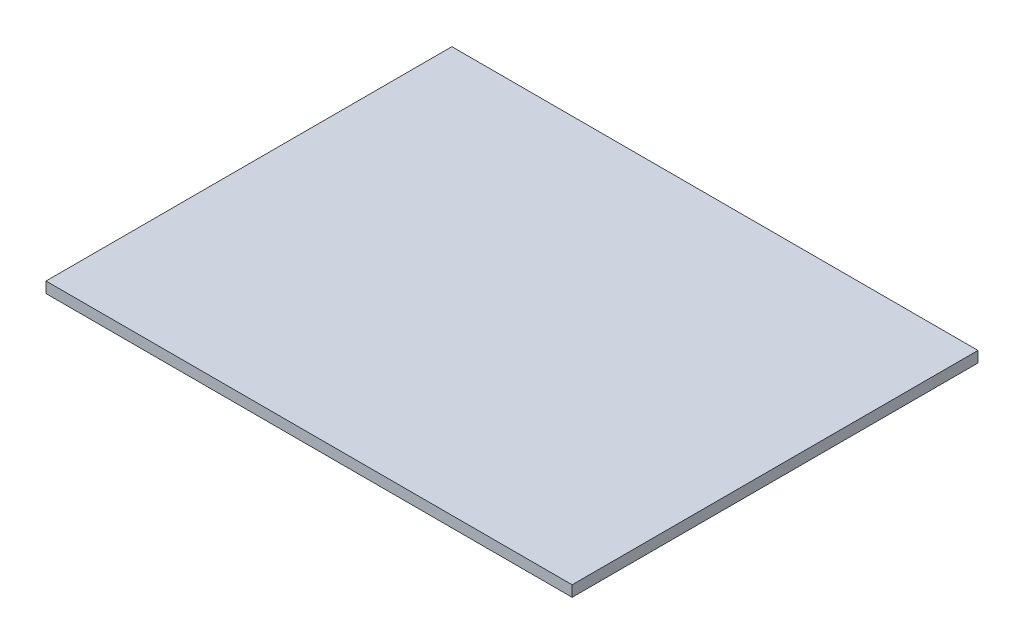
SolidWorks part; units mm, degrees
ref_plane "Plan de face" through (0, 0, 0) normal (0, 0, 1) x (1, 0, 0)
ref_plane "Plan de dessus" through (0, 0, 0) normal (0, 1, 0) x (1, 0, 0)
ref_plane "Plan de droite" through (0, 0, 0) normal (1, 0, 0) x (0, 0, -1)
sketch "Esquisse1" plane through (0, 0, 0) normal (0, 1, 0) x (1, 0, 0)
  line L1 (-35, 27) -> (35, 27)
  line L2 (-35, 27) -> (-35, -27)
  line L3 (-35, -27) -> (35, -27)
  line L4 (35, 27) -> (35, -27)
  line L5 (-35, 27) -> (35, -27) construction
  line L6 (-35, -27) -> (35, 27) construction
  point P0 (0, 0)
  dimension "D1" = 54
  dimension "D2" = 70
extrude "Boss.-Extru.1" add sketch "Esquisse1" along normal blind 1.45
